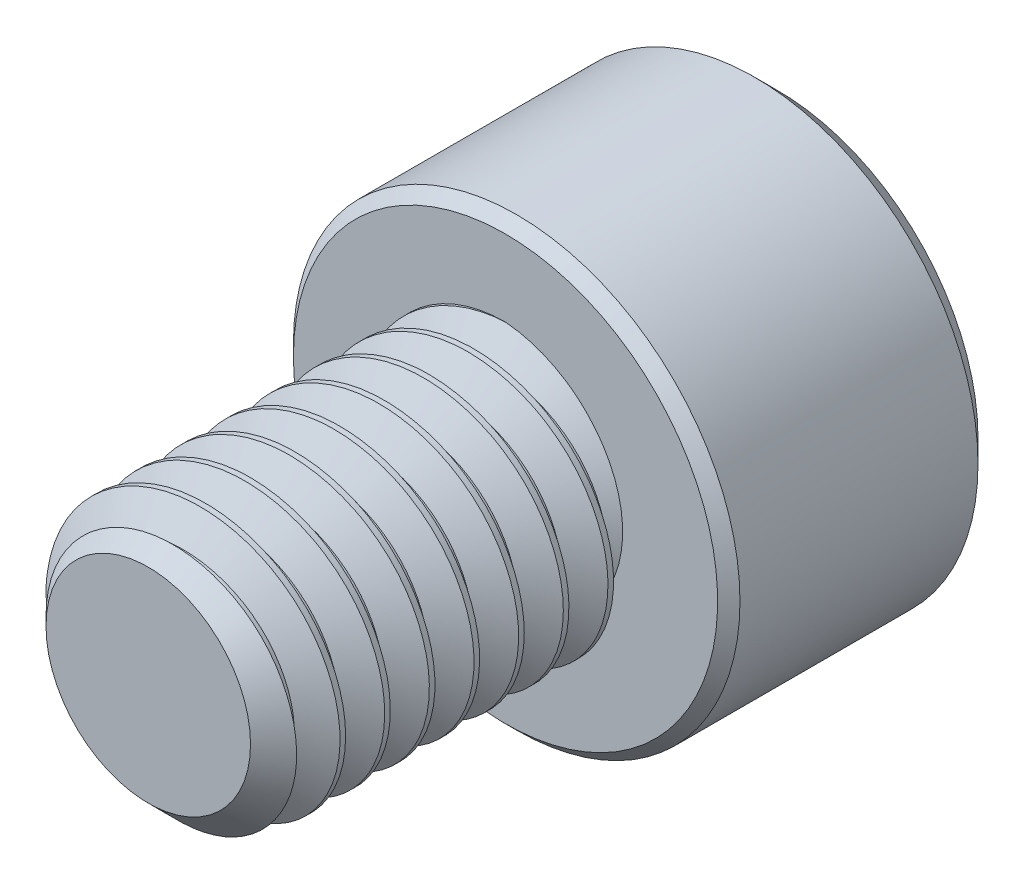
SolidWorks part; units mm, degrees
ref_plane "Front Plane" through (0, 0, 0) normal (0, 0, 1) x (1, 0, 0)
ref_plane "Top Plane" through (0, 0, 0) normal (0, 1, 0) x (1, 0, 0)
ref_plane "Right Plane" through (0, 0, 0) normal (1, 0, 0) x (0, 0, -1)
sketch "Sketch0" plane through (0, 0, 0) normal (1, 0, 0) x (0, 0, -1)
  line L0 (0, 0) -> (6.35, 0) construction
  point P2 (11.176, 0)
  point P4 (0, 0)
  dimension "D1" = 6.35
  dimension "D2" = 4.826
  dimension "Min Thread" = 0
sketch "Sketch1" plane through (0, 0, 0) normal (0, 0, 1) x (1, 0, 0)
  circle A0 centre (0, 0) radius 2.413
  dimension "OD" = 4.826
extrude "Extrude1" add sketch "Sketch1" against normal blind 6.35
sketch "Sketch2" plane through (0, 0, 0) normal (0, 0, 1) x (1, 0, 0)
  circle A0 centre (0, 0) radius 2.413 construction
  circle A1 centre (0, 0) radius 2.413
curve "Helix/Spiral1" pitch 0.7937 height 7.1437 turns 9 parameters "pitch"=0.7937
chamfer "Chamfer3" distance 0.5953 angle 45 1 edges at (2.413, 0, 0)
sketch "Sketch3" plane through (0, 0, 0) normal (1, 0, 0) x (0, 0, -1)
  line L0 (-0.6945, 2.413) -> (-0.3969, 1.8974)
  line L1 (-0.3969, 1.8974) -> (-0.2977, 1.8974)
  line L2 (-0.2977, 1.8974) -> (0, 2.413)
  line L3 (-0.6945, 2.413) -> (0, 2.413)
  line L4 (-0.3473, 2.413) -> (-0.3473, 1.8974) construction
  line L5 (-0.5457, 2.1552) -> (-0.1488, 2.1552) construction
  line L6 (0, 2.413) -> (0, -2.413) construction
  dimension "D1" = 0.0992
  dimension "D2" = 0.3969
  dimension "D3" = 60
sweep "Cut-Sweep1" cut profiles "Sketch3" path "Helix/Spiral1"
sketch "Sketch5" plane through (0, 0, 0) normal (1, 0, 0) x (0, 0, -1)
  line L0 (6.35, -1.9083) -> (6.35, 1.7217) construction
  line L1 (6.35, 2.413) -> (0, 2.413)
  line L2 (6.35, 2.413) -> (6.35, 0)
  line L3 (6.35, 0) -> (-0.8783, 0)
  line L4 (0, 0) -> (6.35, 0) construction
  line L5 (0, 2.413) -> (-0.8783, 0)
  line L6 (0, 0) -> (8.89, 0) construction
  dimension "D1" = 70
  dimension "D3" = 2.54
sketch "Sketch6" plane through (0, 0, -6.35) normal (0, 0, -1) x (-1, 0, 0)
  circle A0 centre (0, 0) radius 3.9688
  dimension "head dia" = 7.9375
extrude "Extrude2" add sketch "Sketch6" along normal blind 4.826
sketch "Sketch7" plane through (0, 0, -11.176) normal (0, 0, -1) x (-1, 0, 0)
  line L1 (0, 2.2914) -> (-1.9844, 1.1457)
  line L2 (-1.9844, 1.1457) -> (-1.9844, -1.1457)
  line L3 (-1.9844, -1.1457) -> (0, -2.2914)
  line L4 (0, -2.2914) -> (1.9844, -1.1457)
  line L5 (1.9844, -1.1457) -> (1.9844, 1.1457)
  line L6 (1.9844, 1.1457) -> (0, 2.2914)
  circle A0 centre (0, 0) radius 1.9844 construction
  dimension "hex dia" = 3.9688
extrude "Cut-Extrude1" cut sketch "Sketch7" against normal blind 2.9766
sketch "Sketch8" plane through (0, 0, -11.176) normal (0, 0, -1) x (-1, 0, 0)
  circle A0 centre (0, 0) radius 2.2914
extrude "Cut-Extrude2" cut sketch "Sketch8" against normal through all draft 45
chamfer "Chamfer1" distance 0.3969 angle 45 1 edges at (-3.9688, 0, -11.176)
chamfer "Chamfer2" distance 0.1984 angle 45 1 edges at (-3.9688, 0, -6.35)
sketch "Sketch9" plane through (0, 0, 0) normal (1, 0, 0) x (0, 0, -1)
  line L0 (0, 2.413) -> (0, -2.413) construction
  line L1 (1.9844, 2.413) -> (1.9844, -2.413) construction
  line L2 (11.176, 3.9688) -> (11.176, -3.9688) construction
  line L3 (6.35, 3.9688) -> (6.35, -3.9688) construction
  line L4 (6.35, 3.7703) -> (6.35, -3.7703) construction
  line L5 (11.176, -3.5719) -> (11.176, 3.5719) construction
  line L6 (6.35, -3.9688) -> (6.35, 3.9688) construction
  line L7 (0, 1.8177) -> (0, -1.8177) construction
  line L8 (-0.6945, 2.413) -> (0, 2.413) construction
  line L9 (1.9844, 0) -> (0, 0) construction
  dimension "D1" = 1.9844
equation "\"D3@Helix/Spiral1\" = \"screw length@Extrude1\"+\"pitch@Helix/Spiral1\""
equation "\"D1@Sketch3\" = \"pitch@Helix/Spiral1\"*.125"
equation "\"D2@Sketch3\" = \"pitch@Helix/Spiral1\"*.5"
equation "\"D1@Cut-Extrude1\" = \"hex dia@Sketch7\"*.75"
equation "\"D1@Chamfer1\" = \"head dia@Sketch6\"*.05"
equation "\"D1@Sketch9\" = \"pitch@Helix/Spiral1\"*2.50"
equation "\"D1@Chamfer2\" = \"D1@Chamfer1\"/2"
equation "\"D1@Chamfer3\" = \"pitch@Helix/Spiral1\"*.750"
equation "\"D1@Sketch0\" = \"screw length@Extrude1\""
equation "\"D2@Sketch0\" = \"head depth@Extrude2\""
